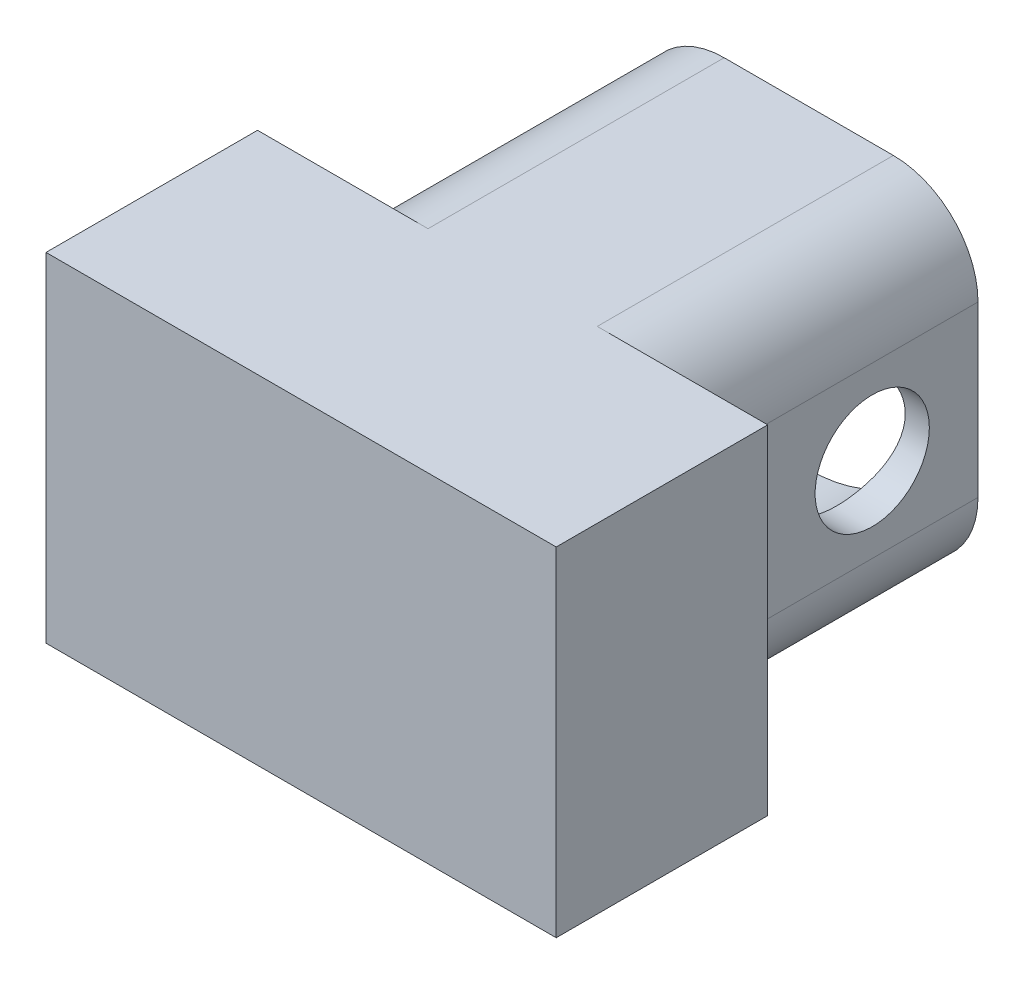
SolidWorks part; units mm, degrees
ref_plane "정면" through (0, 0, 0) normal (0, 0, 1) x (1, 0, 0)
ref_plane "윗면" through (0, 0, 0) normal (0, 1, 0) x (1, 0, 0)
ref_plane "우측면" through (0, 0, 0) normal (1, 0, 0) x (0, 0, -1)
sketch "스케치1" plane through (0, 0, 0) normal (0, 0, 1) x (1, 0, 0)
  line L1 (4, -4) -> (-4, -4)
  line L2 (4, -4) -> (4, 4)
  line L3 (4, 4) -> (-4, 4)
  line L4 (-4, -4) -> (-4, 4)
  line L5 (4, -4) -> (-4, 4) construction
  line L6 (4, 4) -> (-4, -4) construction
  circle A0 centre (0, 0) radius 3.43
  dimension "D1" = 6.86
  dimension "D2" = 8
  dimension "D3" = 8
extrude "보스-돌출1" add sketch "스케치1" along normal blind 7 contours L3 L4 L1 L2
extrude "컷-돌출1" cut sketch "스케치1<3>" along normal blind 6 flip side to cut
sketch "스케치1<3>" plane through (0, 0, 0) normal (0, 0, 1) x (1, 0, 0) same geometry as "스케치1"
sketch "스케치4" plane through (4, 0, 0) normal (1, 0, 0) x (0, 0, -1)
  circle A0 centre (-2.5, 0) radius 1.35
  dimension "D1" = 2.7
  dimension "D2" = 2.5
extrude "컷-돌출2" cut sketch "스케치4" against normal blind 12.6
sketch "스케치6" plane through (0, 0, 7) normal (0, 0, 1) x (1, 0, 0)
  circle A0 centre (0, 0) radius 2.5
  point P0 (0, 0)
  dimension "D1" = 5
sketch "스케치8" plane through (0, 0, 7) normal (0, 0, 1) x (1, 0, 0)
  line L1 (6.03, -4) -> (-6.03, -4)
  line L2 (6.03, -4) -> (6.03, 4)
  line L3 (6.03, 4) -> (-6.03, 4)
  line L4 (-6.03, -4) -> (-6.03, 4)
  line L5 (6.03, -4) -> (-6.03, 4) construction
  line L6 (6.03, 4) -> (-6.03, -4) construction
  point P0 (0, 0)
  dimension "D1" = 8
  dimension "D2" = 12.06
extrude "보스-돌출3" add sketch "스케치8" along normal blind 5
fillet "필렛1" radius 2 4 edges
